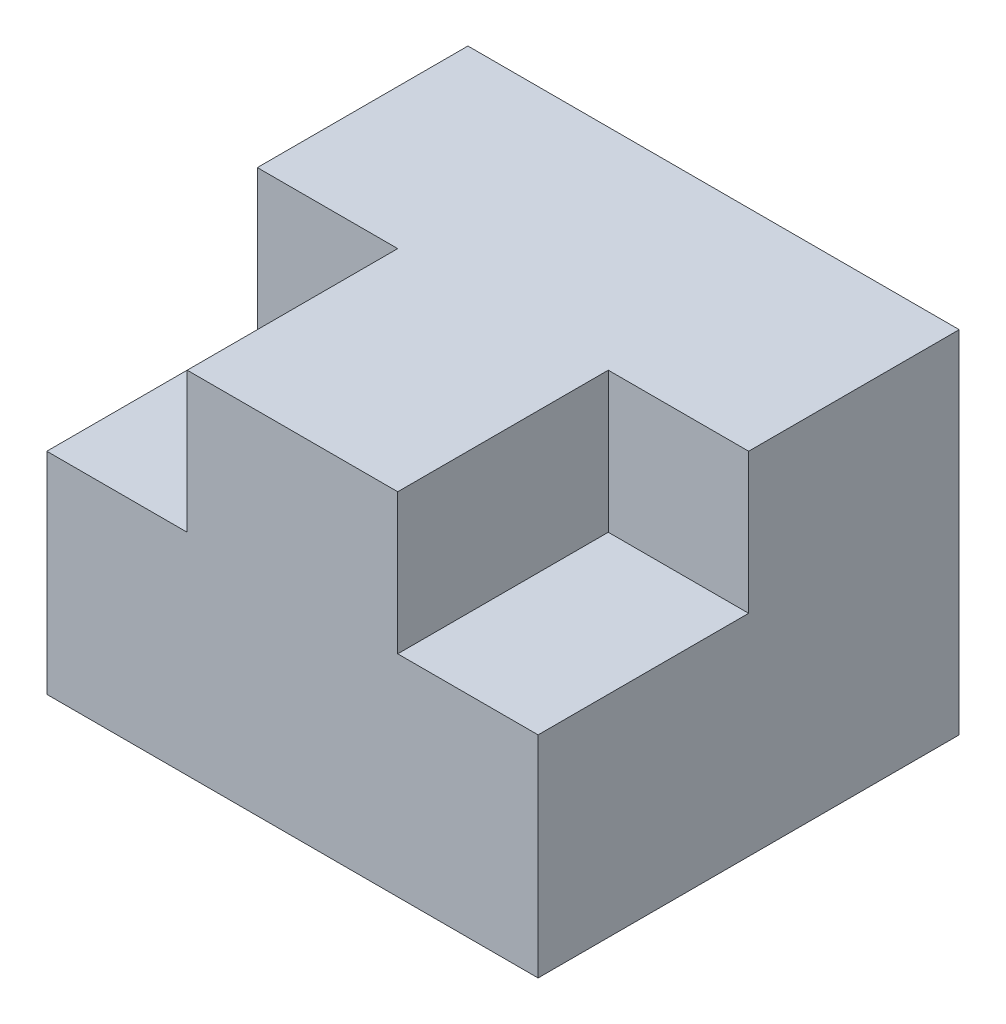
SolidWorks part; units mm, degrees
ref_plane "Front Plane" through (0, 0, 0) normal (0, 0, 1) x (1, 0, 0)
ref_plane "Top Plane" through (0, 0, 0) normal (0, 1, 0) x (1, 0, 0)
ref_plane "Right Plane" through (0, 0, 0) normal (1, 0, 0) x (0, 0, -1)
sketch "Sketch1" plane through (0, 0, 0) normal (0, 0, 1) x (1, 0, 0)
  line L0 (0, 0) -> (35, 0)
  line L1 (35, 0) -> (35, 15)
  line L2 (35, 15) -> (25, 15)
  line L3 (25, 15) -> (25, 25)
  line L4 (25, 25) -> (10, 25)
  line L5 (10, 25) -> (10, 15)
  line L6 (10, 15) -> (0, 15)
  line L7 (0, 15) -> (0, 0)
  line L8 (10, 25) -> (0, 25)
  line L9 (0, 25) -> (0, 15)
  line L10 (25, 25) -> (35, 25)
  line L11 (35, 25) -> (35, 15)
  point P9 (0, 0)
  dimension "D1" = 35
  dimension "D2" = 25
  dimension "D3" = 10
  dimension "D4" = 15
extrude "Boss-Extrude2" add sketch "Sketch1" along normal blind 15 contours L6 L7 L0 L1 L2 L3 L4 L5 region at (17.5, 10.2778, 0)
extrude "Boss-Extrude3" add sketch "Sketch1<7>" against normal blind 15 contours L11 L10 L3 L2 | L6 L7 L0 L1 L2 L3 L4 L5 | L8 L9 L6 L5 region at (17.5, 10.2778, 0) region at (5, 20, 0) region at (30, 20, 0)
sketch "Sketch1<7>" plane through (0, 0, 0) normal (0, 0, 1) x (1, 0, 0) same geometry as "Sketch1"
